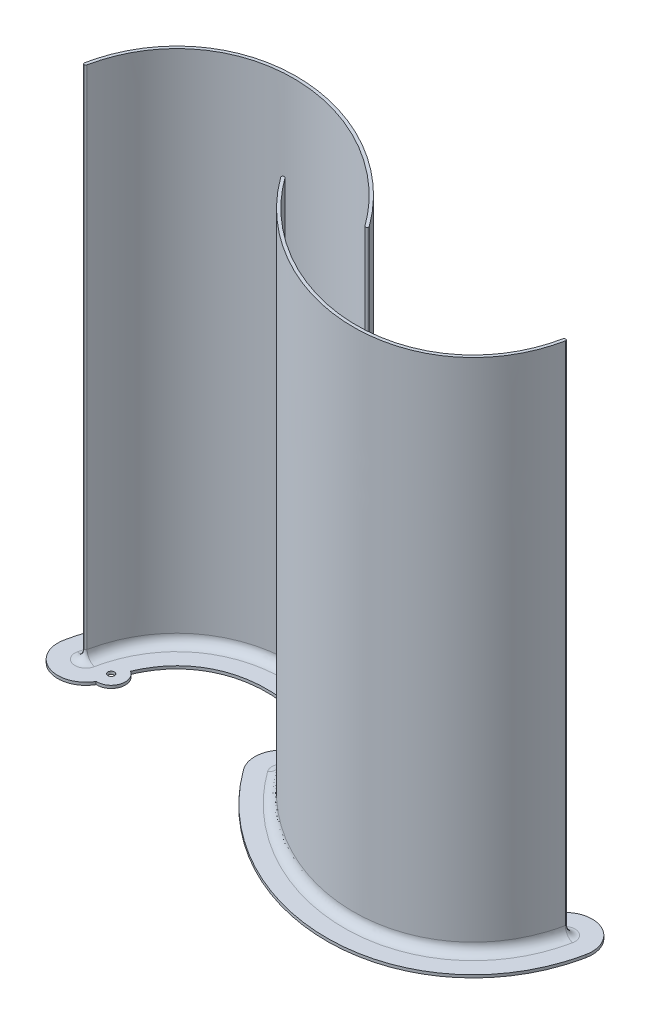
SolidWorks part; units mm, degrees
ref_plane "Front Plane" through (0, 0, 0) normal (0, 0, 1) x (1, 0, 0)
ref_plane "Top Plane" through (0, 0, 0) normal (0, 1, 0) x (1, 0, 0)
ref_plane "Right Plane" through (0, 0, 0) normal (1, 0, 0) x (0, 0, -1)
sketch "Axis" plane through (0, 0, 0) normal (0, 0, 1) x (1, 0, 0)
  line L0 (0, 0) -> (0, 50000) construction
sketch "Geometry" plane through (0, 0, 0) normal (0, 1, 0) x (1, 0, 0)
  line L2 (-218.1407, 67.1512) -> (-84.3738, -78.8297) construction
  line L3 (-84.3738, -78.8297) -> (26.4003, 22.6761) construction
  line L4 (-255, 0) -> (44.9438, 0) construction
  circle A0 centre (0, 0) radius 255 construction
  ellipse E0 centre (-84.3738, -78.8297) end of major axis (-218.1407, 67.1512) minor radius 150.2476 construction
  point P5 (0, 0)
  point P8 (0, 0)
  point P17 (-156.6079, 0)
  dimension "D1" = 510
  dimension "D6" = 299.9438
  dimension "D5" = 198
  dimension "D2" = 106.92
  dimension "D4" = 150.2476
  dimension "D7" = 44.9438
  dimension "D3" = 47.5
sketch "Blade Profile" plane through (0, 0, 0) normal (0, 1, 0) x (1, 0, 0)
  line L0 (-255, 0) -> (44.9438, 0) construction
  arc A0 (46.278, 0.9706) -> (43.6095, -0.9706) centre (44.9438, 0) cw
  arc A1 (-256.6169, 0.3289) -> (-253.3831, -0.3289) centre (-255, 0) ccw
  ellipse E0 centre (-84.3738, -78.8297) end of major axis (49.393, -224.8106) minor radius 150.2476 (44.9438, 0) -> (-255, 0) ccw construction
  spline S0 degree 1 poles (46.278, 0.9706) (-256.6169, 0.3289) knots 0 0 1 1 construction
  spline S1 degree 3 poles (46.278, 0.9706) (43.5717, 4.6909) (37.9655, 11.9819) (25.9538, 26.0046) (3.0365, 48.8321) (-34.2289, 75.621) (-82.8036, 95.9697) (-131.5506, 102.9509) (-169.2211, 97.1299) (-195.8447, 85.7374) (-213.6652, 74.0008) (-228.9817, 59.2976) (-239.4051, 44.8175) (-246.2188, 32.0703) (-250.5429, 21.9779) (-253.4749, 13.161) (-255.4076, 5.8999) (-256.2389, 2.1868) (-256.6169, 0.3289) knots -1.719048 -1.719048 -1.719048 -1.719048 -1.649581 -1.580115 -1.441183 -1.163318 -0.885454 -0.607589 -0.329724 -0.190792 -0.05186 0.087073 0.226005 0.295471 0.364937 0.434404 0.469137 0.50387 0.50387 0.50387 0.50387
  spline S2 degree 1 poles (43.6095, -0.9706) (-253.3831, -0.3289) knots 0 0 1 1 construction
  spline S3 degree 3 poles (43.6095, -0.9706) (40.9374, 2.7025) (35.4025, 9.9008) (23.5416, 23.7474) (0.9122, 46.2881) (-35.8707, 72.7267) (-83.7247, 92.7646) (-131.5777, 99.6029) (-168.3677, 93.9028) (-194.2791, 82.8124) (-211.5963, 71.4061) (-226.4736, 57.1246) (-236.6069, 43.0494) (-243.2396, 30.6416) (-247.4533, 20.8074) (-250.314, 12.2055) (-252.2013, 5.1154) (-253.0138, 1.4865) (-253.3831, -0.3289) knots -1.719048 -1.719048 -1.719048 -1.719048 -1.649581 -1.580115 -1.441183 -1.163318 -0.885454 -0.607589 -0.329724 -0.190792 -0.05186 0.087073 0.226005 0.295471 0.364937 0.434404 0.469137 0.50387 0.50387 0.50387 0.50387
  dimension "D1" = 3.3
sketch "Base profile" plane through (0, 0, 0) normal (0, 1, 0) x (1, 0, 0)
  line L0 (228.0351, 0) -> (-228.0351, 0) construction
  arc A0 (69.2037, 17.6481) -> (20.6838, -17.6481) centre (44.9438, 0) cw
  arc A1 (-284.3978, 5.9806) -> (-225.6022, -5.9806) centre (-255, 0) ccw
  circle A2 centre (0, 0) radius 44.9438
  circle A3 centre (-228.0351, 0) radius 15
  ellipse E0 centre (-84.3738, -78.8297) end of major axis (49.393, -224.8106) minor radius 150.2476 (44.9438, 0) -> (-255, 0) ccw construction
  ellipse E1 centre (-84.3738, -78.8297) end of major axis (-218.1407, 67.1512) minor radius 150.2476 construction
  spline S0 degree 1 poles (69.2037, 17.6481) (-284.3978, 5.9806) knots 0 0 1 1 construction
  spline S1 degree 3 poles (69.2037, 17.6481) (57.2087, 34.1369) (29.5707, 64.7269) (-20.1247, 100.4855) (-74.8907, 123.5043) (-131.3177, 131.7134) (-176.5528, 124.8531) (-209.2942, 110.8665) (-231.4391, 96.2918) (-250.5281, 77.9656) (-263.4444, 60.0062) (-271.8128, 44.3454) (-277.0855, 32.0309) (-281.3362, 19.2472) (-283.4955, 10.4162) (-284.3978, 5.9806) knots -1.719048 -1.719048 -1.719048 -1.719048 -1.441183 -1.163318 -0.885454 -0.607589 -0.329724 -0.190792 -0.05186 0.087073 0.226005 0.295471 0.364937 0.434404 0.50387 0.50387 0.50387 0.50387
  spline S2 degree 1 poles (20.6838, -17.6481) (-225.6022, -5.9806) knots 0 0 1 1 construction
  spline S3 degree 3 poles (20.6838, -17.6481) (18.3064, -14.38) (13.3837, -7.9779) (2.8193, 4.3556) (-17.337, 24.433) (-49.9757, 47.8624) (-91.6374, 65.23) (-131.8108, 70.8404) (-161.0359, 66.1796) (-180.8296, 57.6833) (-193.8224, 49.1151) (-204.9272, 38.4567) (-212.5677, 27.8603) (-217.6456, 18.3673) (-220.9113, 10.7514) (-223.1594, 3.9974) (-224.6563, -1.6238) (-225.3071, -4.5302) (-225.6022, -5.9806) knots -1.719048 -1.719048 -1.719048 -1.719048 -1.649581 -1.580115 -1.441183 -1.163318 -0.885454 -0.607589 -0.329724 -0.190792 -0.05186 0.087073 0.226005 0.295471 0.364937 0.434404 0.469137 0.50387 0.50387 0.50387 0.50387
  point P7 (0, 0)
  dimension "D2" = 456.0702
  dimension "D3" = 30
  dimension "D1" = 60
extrude "Blade" add sketch "Blade Profile" along normal blind 550
extrude "Base" add sketch "Base profile" against normal blind 3 contours S1 A1 S3 A0 | A2 | A3
hole_wizard "M6 Clearance Hole1" positions "Sketch1" profile "Sketch2" hole size "M6" standard "ANSI Metric" end condition through all
sketch "Sketch1" plane through (0, 0, 0) normal (0, 1, 0) x (1, 0, 0)
  point P0 (-228.0351, 0)
sketch "Sketch2" plane through (-228.0351, 0, 0) normal (1, 0, 0) x (0, 0, 1)
  line L0 (0, 0) -> (0, 3)
  line L1 (0, 3) -> (3.5, 3)
  line L2 (3.5, 3) -> (3.5, 0)
  line L5 (3.5, 0) -> (0, 0)
  line L11 (0, -6.35) -> (0, 107.95) construction
  dimension "Thru Hole Dia." = 7
  dimension "Thru Hole Depth" = 3
fillet "Support" radius 10 4 edges at (-255.3289, 0, 1.6169) (45.9144, 0, 1.3343)
pattern_circular "Blade 2" count 2 over 360 about axis through (0, 0, 0) along (0, 1, 0) of bodies 105 102
combine bodies "Savonious" bodies to combine 105 103
equation "\"elli_mayor\"= 198mm"
equation "\"superposition\"= 30"
equation "\"cut_angle\"= 47.5deg"
equation "\"D3@Geometry\"=\"cut_angle\""
equation "\"D5@Geometry\"=\"elli_mayor\""
equation "\"D2@Geometry\" = 0.54 * \"D5@Geometry\""
equation "\"D7@Geometry\"= \"D6@Geometry\" * \"superposition\" / 200"
